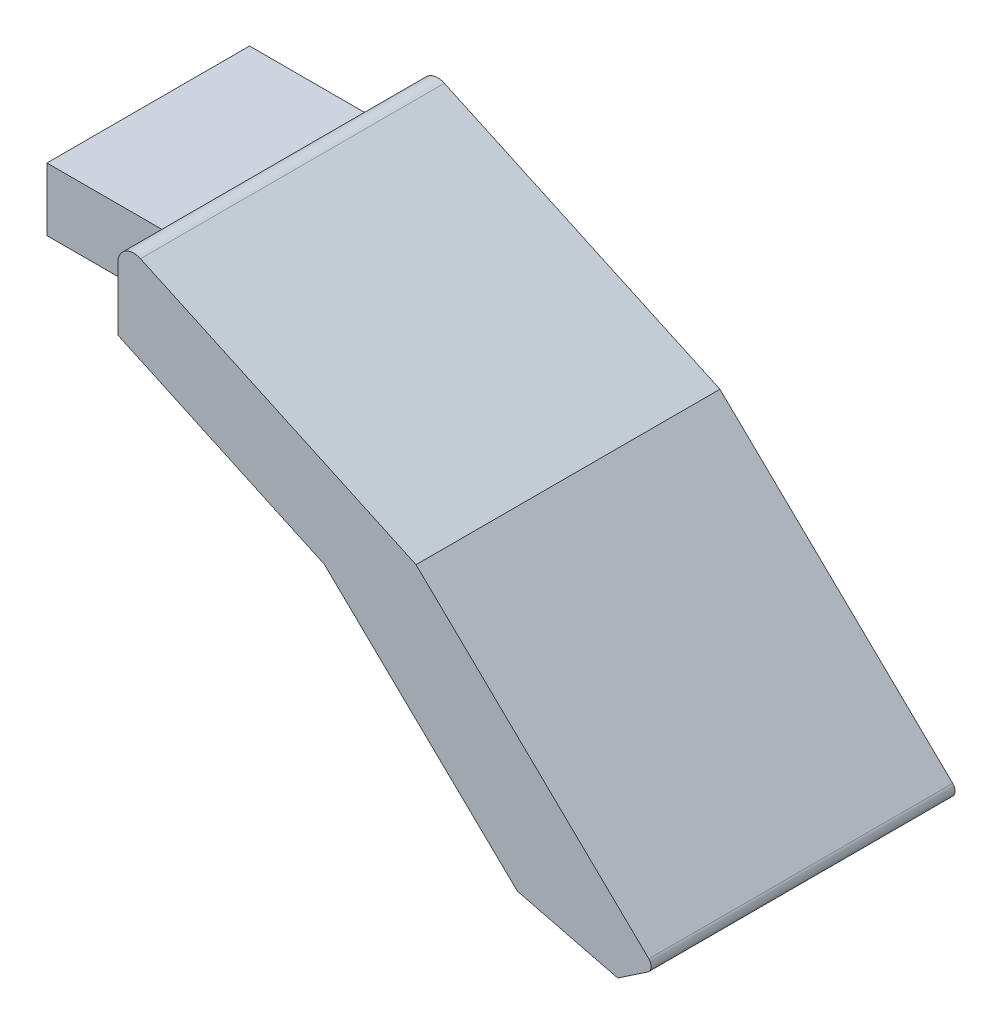
SolidWorks part; units mm, degrees
ref_plane "Plano frontal" through (0, 0, 0) normal (0, 0, 1) x (1, 0, 0)
ref_plane "Plano superior" through (0, 0, 0) normal (0, 1, 0) x (1, 0, 0)
ref_plane "Plano direito" through (0, 0, 0) normal (1, 0, 0) x (0, 0, -1)
sketch "Esboço1" plane through (0, 0, 0) normal (0, 0, 1) x (1, 0, 0)
  line L0 (0, 16.1964) -> (0, 11.2554)
  line L1 (0, 17.4664) -> (0, 16.1964)
  line L2 (29.4384, 6.3393) -> (2.2348, 18.8962)
  line L3 (52.42, -15.861) -> (29.4384, 6.3393)
  line L4 (49.3479, -19.0412) -> (52.3163, -17.041)
  line L5 (39.4448, -16.5704) -> (49.3479, -19.0412)
  line L6 (20.3764, 1.8499) -> (39.4448, -16.5704)
  line L7 (0, 11.2554) -> (20.3764, 1.8499)
  arc A0 (2.2348, 18.8962) -> (0, 17.4664) centre (1.5748, 17.4664) ccw
  arc A1 (52.3163, -17.041) -> (52.42, -15.861) centre (51.8905, -16.4091) ccw
extrude "Ressalto-extrusão1" add sketch "Esboço1" against normal blind 15 and the other way blind 15
sketch "Esboço2" plane through (0, 0, 0) normal (-1, 0, 0) x (0, 0, 1)
  line L0 (-15, 17.4664) -> (15, 11.2554) construction
  line L1 (15, 17.4664) -> (-15, 17.4664) construction
  line L2 (-10, 11.2554) -> (10, 11.2554)
  line L3 (-10, 11.2554) -> (-10, 17.4664)
  line L4 (-10, 17.4664) -> (10, 17.4664)
  line L5 (10, 11.2554) -> (10, 17.4664)
  line L6 (-10, 11.2554) -> (10, 17.4664) construction
  line L7 (-10, 17.4664) -> (10, 11.2554) construction
  point P4 (0, 14.3609)
  point P5 (0, 14.3609)
  dimension "D1" = 20
extrude "Ressalto-extrusão2" add sketch "Esboço2" along normal blind 12
sketch "Esboço4" plane through (0, 0, 10) normal (0, 0, 1) x (1, 0, 0)
  line L0 (-12, 11.2554) -> (0, 11.2554) construction
  line L1 (-4.5, 11.2554) -> (-1.5, 11.2554)
  line L2 (-4.5, 11.2554) -> (-4.5, 5.2554)
  line L3 (-4.5, 5.2554) -> (-1.5, 5.2554)
  line L4 (-1.5, 11.2554) -> (-1.5, 6.2554)
  line L5 (-1.5, 6.2554) -> (-0.7, 6.2554)
  line L6 (-0.7, 6.2554) -> (-0.7, 6.0157)
  line L7 (-0.7, 6.0157) -> (-1.5, 5.2554)
  dimension "D1" = 3
  dimension "D2" = 6
  dimension "D3" = 0.8
  dimension "D4" = 1
  dimension "D5" = 1.5
extrude "Ressalto-extrusão3" add sketch "Esboço4" against normal up to vertex (20 mm away) contours L2 L3 L7 L6 L5 L4 L1 up to point (-12, 11.2554, -10)
sketch "Esboço6" plane through (-4.5, 0, 0) normal (-1, 0, 0) x (0, 0, 1)
  line L0 (-10, 5.2554) -> (10, 5.2554) construction
  line L1 (-10, 11.2554) -> (-7, 11.2554)
  line L2 (-10, 11.2554) -> (-10, 5.2554)
  line L3 (-10, 5.2554) -> (-7, 5.2554)
  line L4 (-7, 11.2554) -> (-7, 5.2554)
  line L6 (10, 11.2554) -> (7, 11.2554)
  line L7 (10, 11.2554) -> (10, 5.2554)
  line L8 (10, 5.2554) -> (7, 5.2554)
  line L9 (7, 11.2554) -> (7, 5.2554)
  dimension "D1" = 3
  dimension "D2" = 3
extrude "Corte-extrusão1" cut sketch "Esboço6" against normal up to vertex (3.8 mm away) up to point (-0.7, 6.2554, 10)
sketch "Esboço7" plane through (10.7604, 11.139, 0) normal (-0.6948, -0.7192, 0) x (0.7192, -0.6948, 0)
  line L0 (13.3699, -15) -> (39.8824, 15) construction
  line L1 (13.3699, 15) -> (13.3699, -15) construction
  line L2 (33.8824, -10) -> (19.3699, -10)
  line L3 (33.8824, -10) -> (33.8824, 10)
  line L4 (33.8824, 10) -> (19.3699, 10)
  line L5 (19.3699, -10) -> (19.3699, 10)
  line L6 (33.8824, -10) -> (19.3699, 10) construction
  line L7 (33.8824, 10) -> (19.3699, -10) construction
  line L8 (13.3699, -15) -> (39.8824, -15) construction
  point P4 (26.6262, 0)
  point P5 (26.6262, 0)
  dimension "D1" = 6
  dimension "D2" = 5
extrude "Ressalto-extrusão4" add sketch "Esboço7" along normal blind 3
